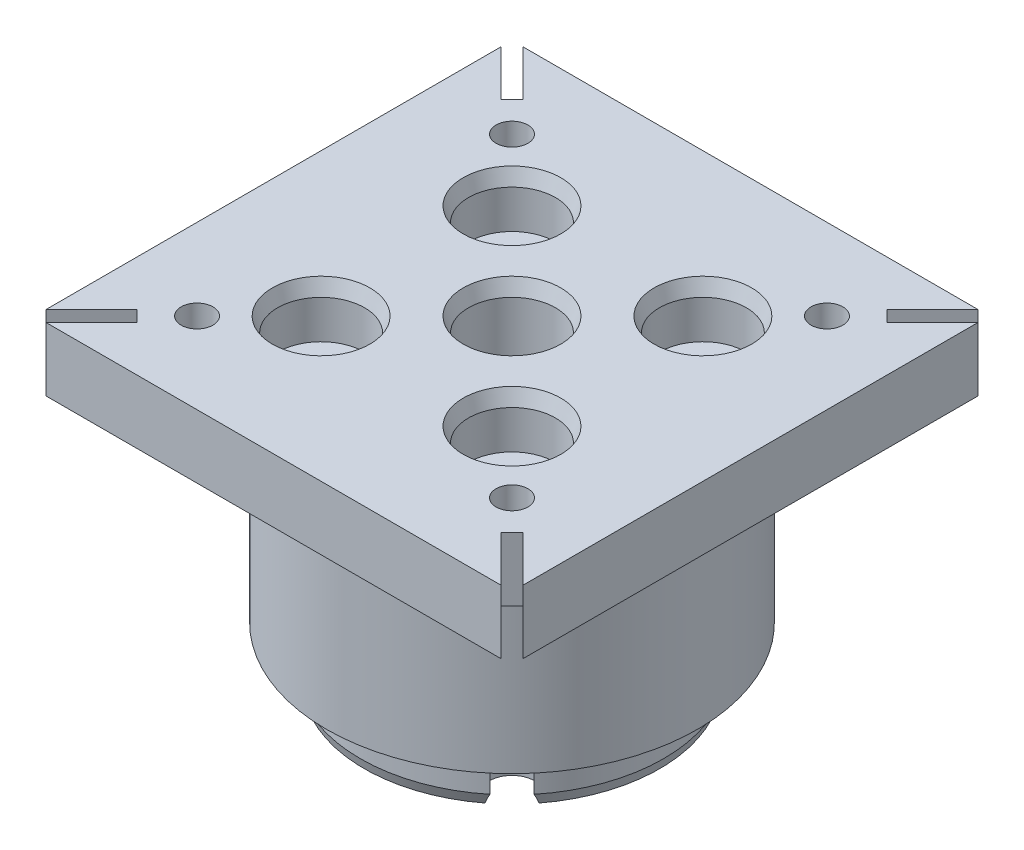
SolidWorks part; units mm, degrees
ref_plane "Спереди" through (0, 0, 0) normal (0, 0, 1) x (1, 0, 0)
ref_plane "Сверху" through (0, 0, 0) normal (0, 1, 0) x (1, 0, 0)
ref_plane "Справа" through (0, 0, 0) normal (1, 0, 0) x (0, 0, -1)
sketch "Sketch1" plane through (0, 0, 0) normal (0, 1, 0) x (1, 0, 0)
  circle A0 centre (0, 0) radius 17.5
  dimension "D1" = 35
extrude "Boss-Extrude1" add sketch "Sketch1" along normal blind 25
sketch "Sketch3" plane through (0, 0, 0) normal (0, -1, 0) x (1, 0, 0)
  circle A0 centre (0, 0) radius 14.3
  circle A1 centre (0, 0) radius 17.5 construction
  dimension "D1" = 3.2
extrude "Boss-Extrude2" add sketch "Sketch3" along normal blind 5
sketch "Sketch4" plane through (0, 25, 0) normal (0, 1, 0) x (1, 0, 0)
  line L1 (-5.2, 5.2) -> (5.2, 5.2) construction
  line L2 (-5.2, 5.2) -> (-5.2, -5.2) construction
  line L3 (-5.2, -5.2) -> (5.2, -5.2) construction
  line L4 (5.2, 5.2) -> (5.2, -5.2) construction
  line L5 (-5.2, 5.2) -> (5.2, -5.2) construction
  line L6 (-5.2, -5.2) -> (5.2, 5.2) construction
  circle A0 centre (0, 0) radius 4.1
  point P0 (0, 0)
  dimension "D2" = 8.2
  dimension "D1" = 10.4
extrude "Cut-Extrude1" cut sketch "Sketch4" against normal through all
sketch "Sketch6" plane through (0, 25, 0) normal (0, 1, 0) x (1, 0, 0)
  line L1 (-9, 9) -> (9, 9) construction
  line L2 (-9, 9) -> (-9, -9) construction
  line L3 (-9, -9) -> (9, -9) construction
  line L4 (9, 9) -> (9, -9) construction
  line L5 (-9, 9) -> (9, -9) construction
  line L6 (-9, -9) -> (9, 9) construction
  circle A0 centre (9, -9) radius 2.1
  circle A1 centre (-9, -9) radius 2.1
  circle A2 centre (-9, 9) radius 2.1
  circle A3 centre (9, 9) radius 2.1
  point P0 (0, 0)
  dimension "D1" = 4.2
  dimension "D2" = 18
extrude "Cut-Extrude2" cut sketch "Sketch6" against normal through all
chamfer "Chamfer1" distance 1 angle 20 4 edges at (14.3, -5, 0) (0, -5, -14.3) (-14.3, -5, 0) (0, -5, 14.3) first distance on face at (12.7, -2.5, 0) first distance on face at (0, -2.5, -12.7) first distance on face at (-12.7, -2.5, 0) first distance on face at (0, -2.5, 12.7)
sketch "Sketch7" plane through (0, 25, 0) normal (0, 1, 0) x (1, 0, 0)
  circle A0 centre (9, 9) radius 4.1
  circle A1 centre (-9, 9) radius 4.1
  circle A2 centre (-9, -9) radius 4.1
  circle A3 centre (9, -9) radius 4.1
  dimension "D1" = 8.2
extrude "Cut-Extrude3" cut sketch "Sketch7" against normal blind 5
chamfer "Chamfer2" distance 0.5 angle 70 1 edges at (0, 25, 4.1) first distance on face at (-9, 25, -4.9)
sketch "Sketch8" plane through (0, 25, 0) normal (0, 1, 0) x (1, 0, 0)
  line L1 (22.5, 22.5) -> (-22.5, 22.5)
  line L2 (22.5, 22.5) -> (22.5, -22.5)
  line L3 (22.5, -22.5) -> (-22.5, -22.5)
  line L4 (-22.5, 22.5) -> (-22.5, -22.5)
  line L5 (22.5, 22.5) -> (-22.5, -22.5) construction
  line L6 (22.5, -22.5) -> (-22.5, 22.5) construction
  circle A0 centre (0, 0) radius 17.5
  circle A1 centre (0, 0) radius 17.5 construction
  circle A2 centre (-14.8492, -14.8492) radius 1.5
  circle A3 centre (-14.8492, 14.8492) radius 1.5
  circle A4 centre (14.8492, 14.8492) radius 1.5
  circle A5 centre (14.8492, -14.8492) radius 1.5
  circle A6 centre (0, 0) radius 21 construction
  circle M12 centre (0, 0) radius 17.5
  dimension "D1" = 3
  dimension "D2" = 42
  dimension "D3" = 45
extrude "Boss-Extrude3" add sketch "Sketch8" against normal blind 6 contours L4 L3 A2 M12 | L3 L2 A5 M12 | L2 L1 A4 M12 | L1 L4 A3 M12 region at (21.8636, 25, 0)
sketch "Sketch10" plane through (0, 25, 0) normal (0, 1, 0) x (1, 0, 0)
  line L0 (-22.5, -22.5) -> (22.5, 22.5) construction
  line L1 (-22.5, 22.5) -> (22.5, -22.5) construction
  line L2 (-18.208, -17.1473) -> (-17.1473, -18.208)
  line L3 (-17.1473, -18.208) -> (-21.4393, -22.5)
  line L4 (22.5, -22.5) -> (-22.5, -22.5) construction
  line L5 (-21.4393, -22.5) -> (-22.5, -22.5)
  line L6 (-22.5, -22.5) -> (-22.5, -21.4393)
  line L7 (-22.5, -21.4393) -> (-18.208, -17.1473)
  line L8 (-22.5, 21.4393) -> (-18.208, 17.1473)
  line L9 (-22.5, 22.5) -> (-22.5, -22.5) construction
  line L10 (-18.208, 17.1473) -> (-17.1473, 18.208)
  line L11 (-17.1473, 18.208) -> (-21.4393, 22.5)
  line L12 (22.5, 22.5) -> (-22.5, 22.5) construction
  line L13 (-21.4393, 22.5) -> (-22.5, 22.5)
  line L14 (-22.5, 22.5) -> (-22.5, 21.4393)
  line L15 (21.4393, 22.5) -> (17.1473, 18.208)
  line L16 (17.1473, 18.208) -> (18.208, 17.1473)
  line L17 (18.208, 17.1473) -> (22.5, 21.4393)
  line L18 (22.5, 22.5) -> (22.5, -22.5) construction
  line L19 (22.5, 21.4393) -> (22.5, 22.5)
  line L20 (22.5, 22.5) -> (21.4393, 22.5)
  line L21 (17.1473, -18.208) -> (18.208, -17.1473)
  line L22 (18.208, -17.1473) -> (22.5, -21.4393)
  line L23 (22.5, -21.4393) -> (22.5, -22.5)
  line L24 (22.5, -22.5) -> (21.4393, -22.5)
  line L25 (21.4393, -22.5) -> (17.1473, -18.208)
  circle A0 centre (-14.8492, -14.8492) radius 1.5 construction
  point P10 (-17.6777, -17.6777)
  point P19 (-17.6777, 17.6777)
  point P26 (17.6777, 17.6777)
  point P33 (17.6777, -17.6777)
  dimension "D1" = 4
  dimension "D2" = 1.5
extrude "Cut-Extrude4" cut sketch "Sketch10" against normal through all
chamfer "Chamfer3" distance 0.5 angle 70 4 edges at (9, 25, -4.9) (-9, 25, -4.9) (-9, 25, 13.1) (9, 25, 13.1) first distance on face at (0, 25, 0)
sketch "Sketch11" plane through (0, -5, 0) normal (0, -1, 0) x (1, 0, 0)
  line L0 (21.4393, 22.5) -> (-21.4393, 22.5) construction
  line L1 (-3.85, 6.6684) -> (-7.7, 0)
  line L2 (-7.7, 0) -> (-3.85, -6.6684)
  line L3 (-3.85, -6.6684) -> (3.85, -6.6684)
  line L4 (3.85, -6.6684) -> (7.7, 0)
  line L5 (7.7, 0) -> (3.85, 6.6684)
  line L6 (3.85, 6.6684) -> (-3.85, 6.6684)
  circle A0 centre (0, 0) radius 7.7 construction
  dimension "D1" = 15.4
extrude "Cut-Extrude5" cut sketch "Sketch11" against normal blind 6.5
